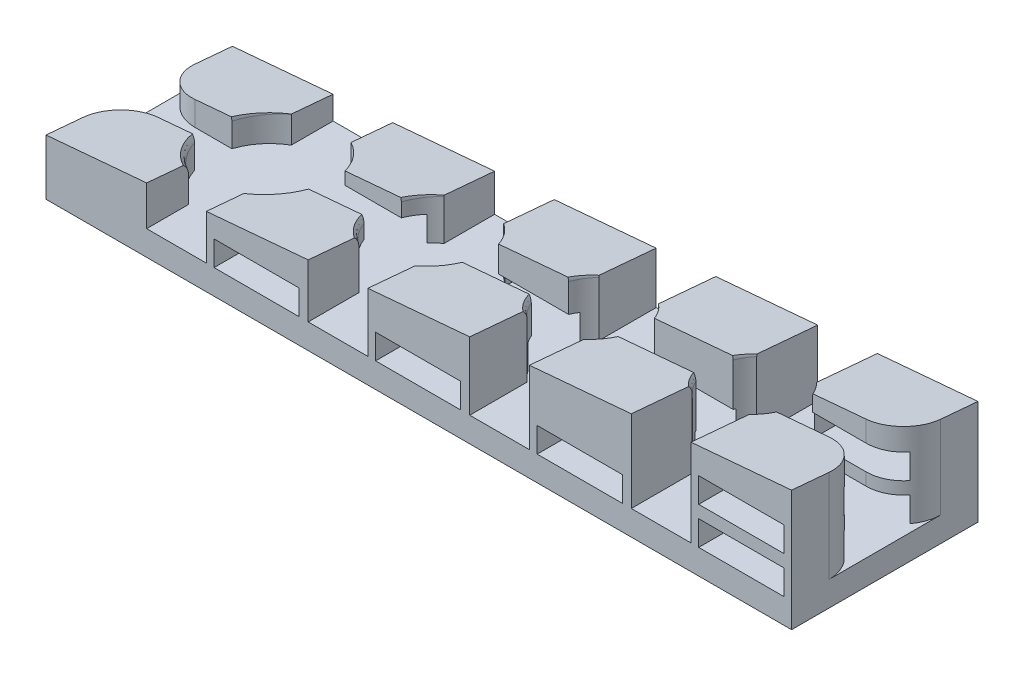
SolidWorks part; units mm, degrees
ref_plane "Front Plane" through (0, 0, 0) normal (0, 0, 1) x (1, 0, 0)
ref_plane "Top Plane" through (0, 0, 0) normal (0, 1, 0) x (1, 0, 0)
ref_plane "Right Plane" through (0, 0, 0) normal (1, 0, 0) x (0, 0, -1)
sketch "Sketch2" plane through (0, 0, 0) normal (0, 1, 0) x (1, 0, 0)
  line L1 (-9.8739, 6.0125) -> (-162.2739, 6.0125)
  line L2 (-9.8739, 6.0125) -> (-9.8739, 44.1125)
  line L3 (-9.8739, 44.1125) -> (-162.2739, 44.1125)
  line L4 (-162.2739, 6.0125) -> (-162.2739, 44.1125)
  dimension "D1" = 152.4
  dimension "D2" = 38.1
extrude "Boss-Extrude1" add sketch "Sketch2" along normal blind 25.4
sketch "Sketch3" plane through (0, 25.4, 0) normal (0, 1, 0) x (1, 0, 0)
  line L0 (-162.2739, 25.0625) -> (-9.8739, 25.0625) construction
  line L1 (-162.2739, 44.1125) -> (-162.2739, 6.0125) construction
  line L2 (-9.8739, 6.0125) -> (-9.8739, 44.1125) construction
  circle A0 centre (-36.5439, 25.0625) radius 8.9789
  circle A1 centre (-69.5639, 25.0625) radius 9.5504
  circle A2 centre (-102.5839, 25.0625) radius 10.6299
  circle A3 centre (-135.6039, 25.0625) radius 12.1539
  dimension "D1" = 17.9578
  dimension "D2" = 19.1008
  dimension "D3" = 21.2598
  dimension "D4" = 24.3078
  dimension "D5" = 26.67
  dimension "D6" = 33.02
  dimension "D7" = 33.02
  dimension "D8" = 33.02
  dimension "D9" = 26.67
extrude "Cut-Extrude1" cut sketch "Sketch3" against normal offset from surface (20.32 mm away) 5.08 up to face at (-86.0739, 0, -25.0625)
ref_plane "Plane1" through (-3.438, 39.2963, 0) normal (-0.0872, 0.9962, 0) x (0.9962, 0.0872, 0)
sketch "Sketch6" plane through (-3.438, 39.2963, 0) normal (-0.0872, 0.9962, 0) x (0.9962, 0.0872, 0)
  line L1 (-170.4577, 63.4342) -> (10.814, 63.4342)
  line L2 (-170.4577, 63.4342) -> (-170.4577, -17.9499)
  line L3 (-170.4577, -17.9499) -> (10.814, -17.9499)
  line L4 (10.814, 63.4342) -> (10.814, -17.9499)
extrude "Cut-Extrude12" cut sketch "Sketch6" against normal blind 13.97
sketch "Sketch7" plane through (0, 0, -6.0125) normal (0, 0, 1) x (1, 0, 0)
  line L1 (-42.6399, 157.9878) -> (-30.4479, 157.9878)
  line L2 (-42.6399, 157.9878) -> (-42.6399, 5.08)
  line L3 (-42.6399, 5.08) -> (-30.4479, 5.08)
  line L4 (-30.4479, 157.9878) -> (-30.4479, 5.08)
  line L7 (-9.8739, 24.7099) -> (-9.8739, 0) construction
  line L9 (-162.2739, 0) -> (-9.8739, 0) construction
  dimension "D1" = 20.574
  dimension "D2" = 12.192
  dimension "D3" = 5.08
extrude "Cut-Extrude13" cut sketch "Sketch7" against normal blind 59.69 contours L2 L3 L4 L1
pattern_linear "LPattern1" count 4 spacing 33.02 along (-1, 0, 0) of "Cut-Extrude13"
sketch "Sketch8" plane through (-9.8739, 0, 0) normal (1, 0, 0) x (0, 0, -1)
  line L0 (6.0125, 0) -> (44.1125, 0) construction
  line L1 (21.2525, 5.08) -> (28.8725, 5.08)
  line L2 (21.2525, 5.08) -> (21.2525, 164.0227)
  line L3 (21.2525, 164.0227) -> (28.8725, 164.0227)
  line L4 (28.8725, 5.08) -> (28.8725, 164.0227)
  line L5 (44.1125, 24.7099) -> (44.1125, 0) construction
  line L6 (6.0125, 24.7099) -> (6.0125, 0) construction
  dimension "D1" = 5.08
  dimension "D2" = 7.62
  dimension "D3" = 15.24
  dimension "D4" = 15.24
extrude "Cut-Extrude14" cut sketch "Sketch8" against normal blind 199.136 contours L3 L4 L1 L2
fillet "Fillet1" radius 2.54 16 edges at (-77.1988, 18.8197, -19.3251) (-77.1988, 18.8197, -30.7999) (-61.9289, 20.1557, -30.7999) (-61.9289, 20.1557, -19.3251) (-43.7919, 21.7425, -30.3622) (-29.2959, 23.0107, -30.3622) (-43.7919, 21.7425, -19.7628) (-29.2959, 23.0107, -19.7628) (-110.9598, 15.866, -31.6077) (-110.9598, 15.866, -18.5173) (-94.208, 17.3316, -18.5173) (-94.208, 17.3316, -31.6077) (-126.1696, 14.5354, -17.4002) (-126.1696, 14.5354, -32.7248) (-145.0382, 12.8846, -17.4002) (-145.0382, 12.8846, -32.7248)
sketch "Sketch9" plane through (0, 0, -6.0125) normal (0, 0, 1) x (1, 0, 0)
  line L1 (-28.8604, 10.16) -> (-11.4614, 10.16)
  line L2 (-28.8604, 10.16) -> (-28.8604, 5.08)
  line L3 (-28.8604, 5.08) -> (-11.4614, 5.08)
  line L4 (-11.4614, 10.16) -> (-11.4614, 5.08)
  line L6 (-30.4479, 22.9099) -> (-30.4479, 5.08) construction
  line L7 (-9.8739, 24.7099) -> (-9.8739, 0) construction
  line L8 (-162.2739, 0) -> (-9.8739, 0) construction
  dimension "D1" = 1.5875
  dimension "D2" = 1.5875
  dimension "D3" = 5.08
  dimension "D4" = 5.08
extrude "Cut-Extrude15" cut sketch "Sketch9" against normal blind 199.136
fillet "Fillet2" radius 7.62 4 edges at (-162.2739, 8.2283, -21.2525) (-162.2739, 8.2283, -28.8725) (-9.8739, 14.895, -21.2525) (-9.8739, 14.895, -28.8725)
ref_plane "Plane2" through (-2.249, 25.7068, -2.2576) normal (-0.0868, 0.9924, -0.0872) x (0.9962, 0.0872, 0)
sketch "Sketch10" plane through (-2.249, 25.7068, -2.2576) normal (-0.0868, 0.9924, -0.0872) x (0.9962, 0.0872, 0)
  line L1 (-199.7047, -26.8172) -> (43.2114, -26.8172)
  line L2 (-199.7047, -26.8172) -> (-199.7047, 85.1814)
  line L3 (-199.7047, 85.1814) -> (43.2114, 85.1814)
  line L4 (43.2114, -26.8172) -> (43.2114, 85.1814)
extrude "Cut-Extrude16" cut sketch "Sketch10" along normal blind 16.256 contours L1 L4 L3 L2
pattern_linear "LPattern2" count 4 spacing 33.02 along (-1, 0, 0) of "Cut-Extrude15"
pattern_linear "LPattern3" count 2 spacing 7.62 along (0, 1, 0) of "Cut-Extrude15"
